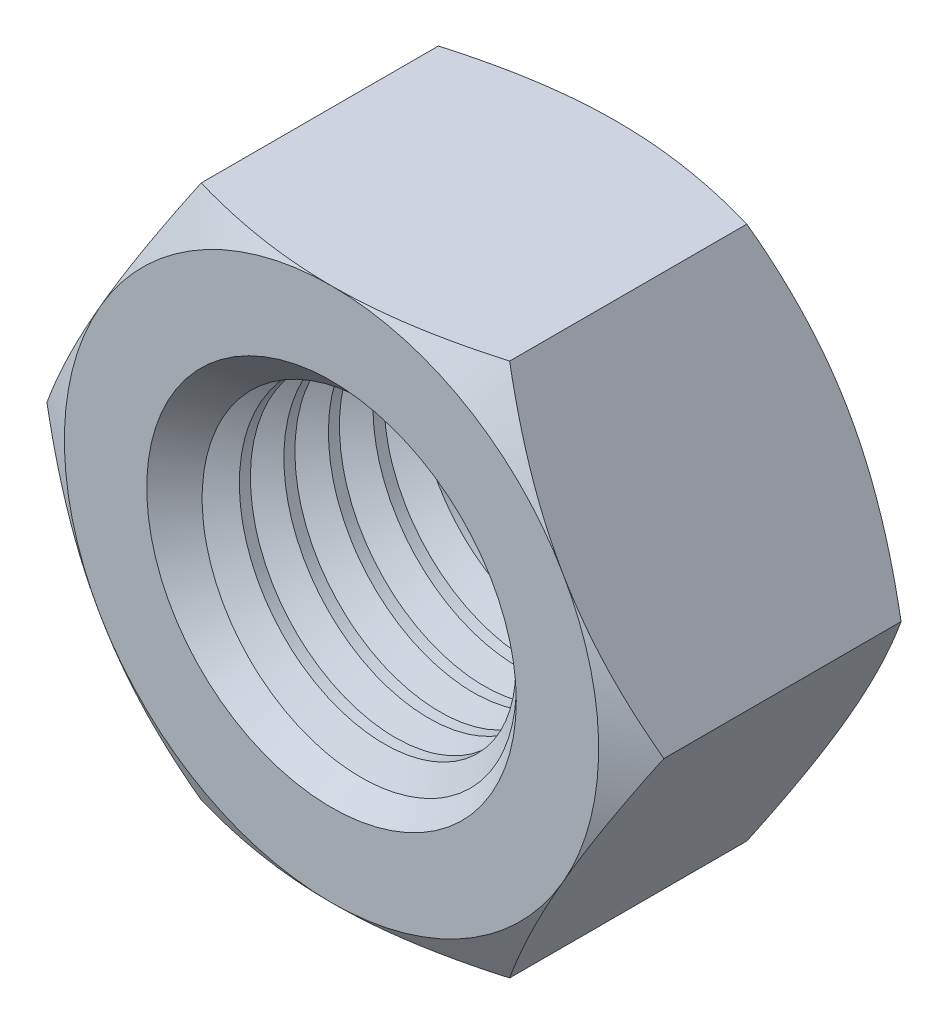
SolidWorks part; units mm, degrees
ref_plane "Front" through (0, 0, 0) normal (0, 0, 1) x (1, 0, 0)
ref_plane "Top" through (0, 0, 0) normal (0, 1, 0) x (1, 0, 0)
ref_plane "Right" through (0, 0, 0) normal (1, 0, 0) x (0, 0, -1)
sketch "Çizim1" plane through (0, 0, 0) normal (0, 0, 1) x (1, 0, 0)
  line L1 (17.3205, 0) -> (8.6603, 15)
  line L2 (8.6603, 15) -> (-8.6603, 15)
  line L3 (-8.6603, 15) -> (-17.3205, 0)
  line L4 (-17.3205, 0) -> (-8.6603, -15)
  line L5 (-8.6603, -15) -> (8.6603, -15)
  line L6 (8.6603, -15) -> (17.3205, 0)
  circle A0 centre (0, 0) radius 15 construction
  point P1 (0, 0)
  dimension "D1" = 30
extrude "Yükseklik-Ekstrüzyon1" add sketch "Çizim1" along normal blind 16
sketch "Çizim2" plane through (0, 0, 16) normal (0, 0, 1) x (1, 0, 0)
  circle A0 centre (0, 0) radius 15
extrude "Kes-Ekstrüzyon1" cut sketch "Çizim2" against normal blind 16 draft 60 flip side to cut
sketch "Çizim3" plane through (0, 0, 0) normal (0, 0, -1) x (-1, 0, 0)
  circle A0 centre (0, 0) radius 15
extrude "Kes-Ekstrüzyon2" cut sketch "Çizim3" against normal blind 16 draft 60 flip side to cut
sketch "Çizim4" plane through (0, 0, 0) normal (0, 0, -1) x (-1, 0, 0)
  circle A0 centre (0, 0) radius 8.375
  dimension "D1" = 16.75
extrude "Kes-Ekstrüzyon3" cut sketch "Çizim4" against normal blind 16
chamfer "Pah1" distance 2 angle 45 2 edges at (-8.375, 0, 16) (-8.375, 0, 0)
sketch "Çizim5" plane through (0, 0, 0) normal (0, 0, -1) x (-1, 0, 0)
  circle A0 centre (0, 0) radius 8.375
  dimension "D1" = 16.75
curve "Helis/Spiral1" pitch 2.5 height 19 radius 8.375 centre (0, 0, 0) axis (0, 0, 1) start towards (1, 0, 0)
ref_plane "Düzlem1" through (-6.7755, -4.9227, 19) normal (0.5871, -0.8081, 0.0475) x (-0.8095, -0.5861, 0.0344)
sketch "Çizim6" plane through (-6.7755, -4.9227, 19) normal (0.5871, -0.8081, 0.0475) x (-0.8095, -0.5861, 0.0344)
  line L0 (-0.4989, -1.2262) -> (-0.4989, 1.2262)
  line L1 (1.625, 0) -> (-0.4989, 1.2262)
  line L3 (-0.4989, -1.2262) -> (1.625, 0)
  line L5 (-0.8125, 1.4073) -> (-0.8125, 0) [skipped]
  circle A0 centre (0, 0) radius 0.8125 construction
  dimension "D1" = 1.625
sweep "Kes-Süpür1" cut profiles "Çizim6" path "Helis/Spiral1" align with end faces yes
